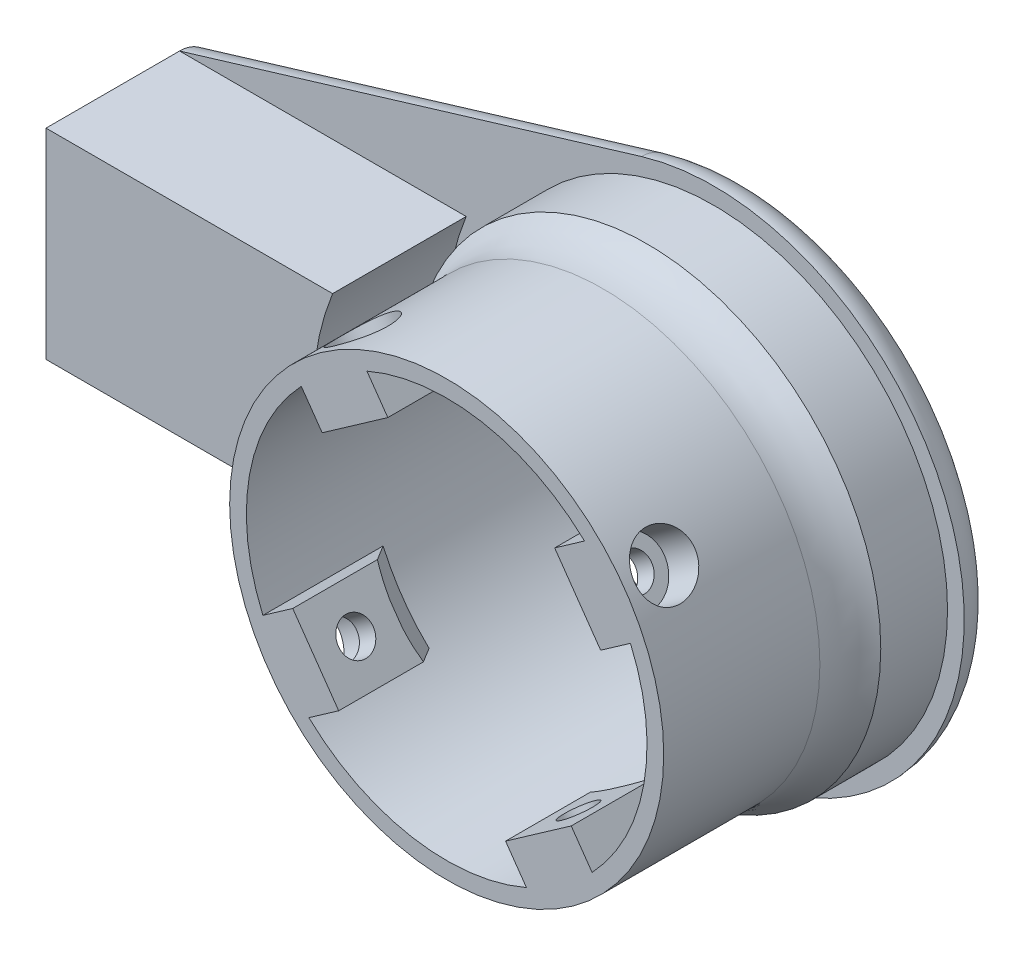
SolidWorks part; units mm, degrees
ref_plane "Plan de face" through (0, 0, 0) normal (0, 0, 1) x (1, 0, 0)
ref_plane "Plan de dessus" through (0, 0, 0) normal (0, 1, 0) x (1, 0, 0)
ref_plane "Plan de droite" through (0, 0, 0) normal (1, 0, 0) x (0, 0, -1)
sketch "Esquisse1" plane through (0, 0, 0) normal (0, 0, 1) x (1, 0, 0)
  line L0 (-1000, 0) -> (49000, 0) construction
  line L1 (-10.8475, 35.8968) -> (-80, 15)
  line L2 (-80, 15) -> (-80, -15)
  line L3 (-10.8475, -35.8968) -> (-80, -15)
  arc A0 (-10.8475, -35.8968) -> (-10.8475, 35.8968) centre (0, 0) ccw
  circle A1 centre (0, 0) radius 30
  point P9 (-80, 0)
  dimension "D1" = 75
  dimension "D4" = 60
  dimension "D2" = 15
  dimension "D3" = 80
extrude "Boss.-Extru.1" add sketch "Esquisse1" along normal blind 5
sketch "Esquisse6" plane through (0, 0, 5) normal (0, 0, 1) x (1, 0, 0)
  circle A0 centre (0, 0) radius 35
  circle A1 centre (0, 0) radius 30
  dimension "D1" = 70
  dimension "D2" = 60
extrude "Boss.-Extru.6" add sketch "Esquisse6" along normal blind 10
sketch "Esquisse7" plane through (0, 0, 15) normal (0, 0, 1) x (1, 0, 0)
  circle A0 centre (0, 0) radius 30
  circle A1 centre (0, 0) radius 32.5
  dimension "D1" = 65
extrude "Boss.-Extru.8" add sketch "Esquisse7" along normal blind 30
fillet "Congé2" radius 10 1 edges at (32.5, 0, 15)
sketch "Esquisse8" plane through (0, 0, 5) normal (0, 0, 1) x (1, 0, 0)
  line L0 (-80, 15) -> (-37.081, 15)
  line L1 (-1000, 0) -> (49000, 0) construction
  line L2 (-80, 15) -> (-80, -15)
  line L3 (-80, 15) -> (-80, -15) construction
  line L4 (-80, -15) -> (-37.081, -15)
  arc A0 (-37.081, 15) -> (-37.081, -15) centre (0, 0) ccw
  point P12 (-80, 0)
  dimension "D1" = 80
extrude "Boss.-Extru.9" add sketch "Esquisse8" along normal blind 20
sketch "Esquisse9" plane through (0, 0, 45) normal (0, 0, 1) x (1, 0, 0)
  line L7 (-1000, 0) -> (49000, 0) construction
  line L8 (0, 0) -> (-36070.1927, -25256.6208) construction
  line L11 (-29.6063, -13.4059) -> (-22.7234, -23.2357)
  line L13 (-29.6063, -13.4059) -> (-23.0531, -8.8173)
  line L15 (-23.0531, -8.8173) -> (-16.1701, -18.6471)
  line L17 (-22.7234, -23.2357) -> (-16.1701, -18.6471)
  circle A2 centre (0, 0) radius 32.5 construction
  point P0 (0, 0)
  point P1 (0, 0)
  point P22 (0, 0)
  dimension "D2" = 12
  dimension "D4" = 35
  dimension "D5" = 8
extrude "Boss.-Extru.10" add sketch "Esquisse9" against normal blind 12
chamfer "Chanfrein1" distance 6 angle 45 1 edges at (-24.5746, -17.2073, 33)
fillet "Congé3" radius 5 3 edges at (37.5, 0, 0) (-45.4237, 25.4484, 0) (-45.4237, -25.4484, 0)
sketch "Esquisse10" plane through (-19.6116, -13.7322, 0) normal (0.8192, 0.5736, 0) x (0, 0, -1)
  line L0 (-45, 32.5) -> (-45, -32.5) construction
  circle A0 centre (-39, 0) radius 4.5
  dimension "D1" = 9
  dimension "D2" = 6
extrude "Enlèv. mat.-Extru.1" cut sketch "Esquisse10" against normal up to next
sketch "Esquisse11" plane through (-19.6116, -13.7322, 0) normal (0.8192, 0.5736, 0) x (0, 0, -1)
  line L0 (-45, 32.5) -> (-45, -32.5) construction
  circle A0 centre (-39, 0) radius 2.6
  circle A1 centre (-39, 0) radius 4.5
  dimension "D2" = 5.2
  dimension "D3" = 9
  dimension "D1" = 6
extrude "Boss.-Extru.11" add sketch "Esquisse11" against normal blind 3
pattern_circular "Répétition circulaire1" count 4 every 90 about axis through (0, 0, 45) along (0, 0, 1) of "Chanfrein1", "Boss.-Extru.10", "Boss.-Extru.11", "Enlèv. mat.-Extru.1"
